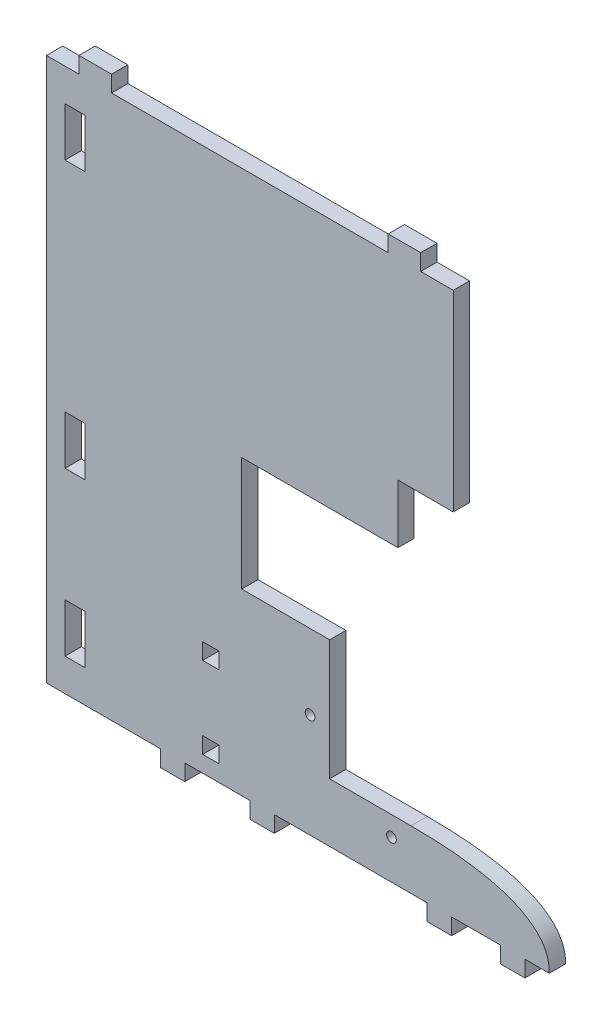
SolidWorks part; units mm, degrees
ref_plane "Plan de face" through (0, 0, 0) normal (0, 0, 1) x (1, 0, 0)
ref_plane "Plan de dessus" through (0, 0, 0) normal (0, 1, 0) x (1, 0, 0)
ref_plane "Plan de droite" through (0, 0, 0) normal (1, 0, 0) x (0, 0, -1)
sketch "Esquisse1" plane through (0, 0, 0) normal (0, 0, 1) x (1, 0, 0)
  line L1 (0, 0) -> (37, 0)
  line L2 (0, 0) -> (0, 55)
  line L3 (0, 55) -> (12, 55)
  line L4 (37, 0) -> (37, 18)
  line L6 (12, 55) -> (12, 18)
  line L7 (12, 18) -> (37, 18)
  circle A0 centre (6, 32) radius 1.5
  circle A1 centre (31, 12) radius 1.5
  dimension "D3" = 20
  dimension "D4" = 3
  dimension "D1" = 6
  dimension "D2" = 55
  dimension "D5" = 12
  dimension "D7" = 25
  dimension "D8" = 6
  dimension "D9" = 6
extrude "Boss.-Extru.1" add sketch "Esquisse1" along normal blind 5
sketch "Esquisse2" plane through (0, 0, 5) normal (0, 0, 1) x (1, 0, 0)
  line L0 (37, 18) -> (12, 18) construction
  line L1 (37, 0) -> (42, 0)
  line L2 (37, 0) -> (37, 18)
  line L3 (49.5, 0) -> (64.5, 0)
  line L4 (12, 55) -> (0, 55) construction
  line L5 (72, 0) -> (72, -5)
  line L6 (72, -5) -> (64.5, -5)
  line L7 (64.5, 0) -> (64.5, -5)
  line L8 (72, 0) -> (79.5, 0)
  line L9 (49.5, 0) -> (49.5, -5)
  line L10 (49.5, -5) -> (42, -5)
  line L11 (42, 0) -> (42, -5)
  line L12 (0, 0) -> (-5, 0)
  line L13 (0, 0) -> (0, 55)
  line L14 (0, 55) -> (-15, 55)
  line L15 (40, 167) -> (50, 167)
  line L16 (-12.5, 0) -> (-32.5, 0)
  line L17 (-40, 0) -> (-40, -5)
  line L18 (-15, 55) -> (-15, 90)
  line L19 (-40, -5) -> (-32.5, -5)
  line L20 (-75, 0) -> (-75, 167)
  line L21 (-75, 167) -> (-65, 167)
  line L22 (-32.5, 0) -> (-32.5, -5)
  line L23 (33, 90) -> (-15, 90)
  line L24 (50, 167) -> (50, 108)
  line L25 (-12.5, 0) -> (-12.5, -5)
  line L26 (-12.5, -5) -> (-5, -5)
  line L27 (-5, 0) -> (-5, -5)
  line L28 (-40, 0) -> (-75, 0)
  line L29 (-65, 167) -> (-65, 172)
  line L30 (-65, 172) -> (-55, 172)
  line L31 (-55, 167) -> (-55, 172)
  line L32 (-55, 167) -> (30, 167)
  line L33 (40, 167) -> (40, 172)
  line L34 (40, 172) -> (30, 172)
  line L35 (30, 167) -> (30, 172)
  line L36 (-69.2981, 10) -> (-63.1592, 10)
  line L37 (-69.2981, 10) -> (-69.2981, 25)
  line L38 (33, 90) -> (33, 108)
  line L39 (33, 108) -> (50, 108)
  line L40 (-63.1592, 10) -> (-63.1592, 25)
  line L41 (-69.2981, 25) -> (-63.1592, 25)
  line L42 (-69.2981, 10) -> (-69.2981, 0) construction
  line L43 (-63.1592, 25) -> (-63.1592, 10) construction
  line L45 (-69.2981, 75) -> (-63.1592, 75)
  line L46 (-69.2981, 75) -> (-69.2981, 60)
  line L47 (-69.2981, 60) -> (-63.1592, 60)
  line L48 (-63.1592, 75) -> (-63.1592, 60)
  line L49 (-69.2981, 142) -> (-63.1592, 142)
  line L50 (-69.2981, 142) -> (-69.2981, 157)
  line L51 (-69.2981, 157) -> (-63.1592, 157)
  line L52 (-63.1592, 142) -> (-63.1592, 157)
  line L53 (-22, 5) -> (-27, 5)
  line L54 (-22, 5) -> (-22, 10)
  line L55 (-22, 10) -> (-27, 10)
  line L56 (-27, 5) -> (-27, 10)
  line L57 (-27, 35) -> (-22, 35)
  line L58 (-27, 35) -> (-27, 30)
  line L59 (-27, 30) -> (-22, 30)
  line L60 (-22, 35) -> (-22, 30)
  spline S0 degree 3 poles (37, 18) (79.2395, 18) (79.5, 3.8743) (79.5, 0) knots 0 0 0 0 1 1 1 1
  dimension "D1" = 42.5
  dimension "D2" = 7.5
  dimension "D3" = 5
  dimension "D4" = 5
  dimension "D5" = 15
  dimension "D6" = 15
  dimension "D7" = 35
  dimension "D8" = 167
  dimension "D9" = 18
  dimension "D10" = 5
  dimension "D11" = 20
  dimension "D12" = 75
  dimension "D13" = 50
  dimension "D14" = 5
  dimension "D15" = 10
  dimension "D16" = 10
  dimension "D17" = 10
  dimension "D18" = 17
  dimension "D19" = 10
  dimension "D20" = 15
  dimension "D21" = 35
  dimension "D22" = 10
extrude "Boss.-Extru.2" add sketch "Esquisse2" against normal blind 5
